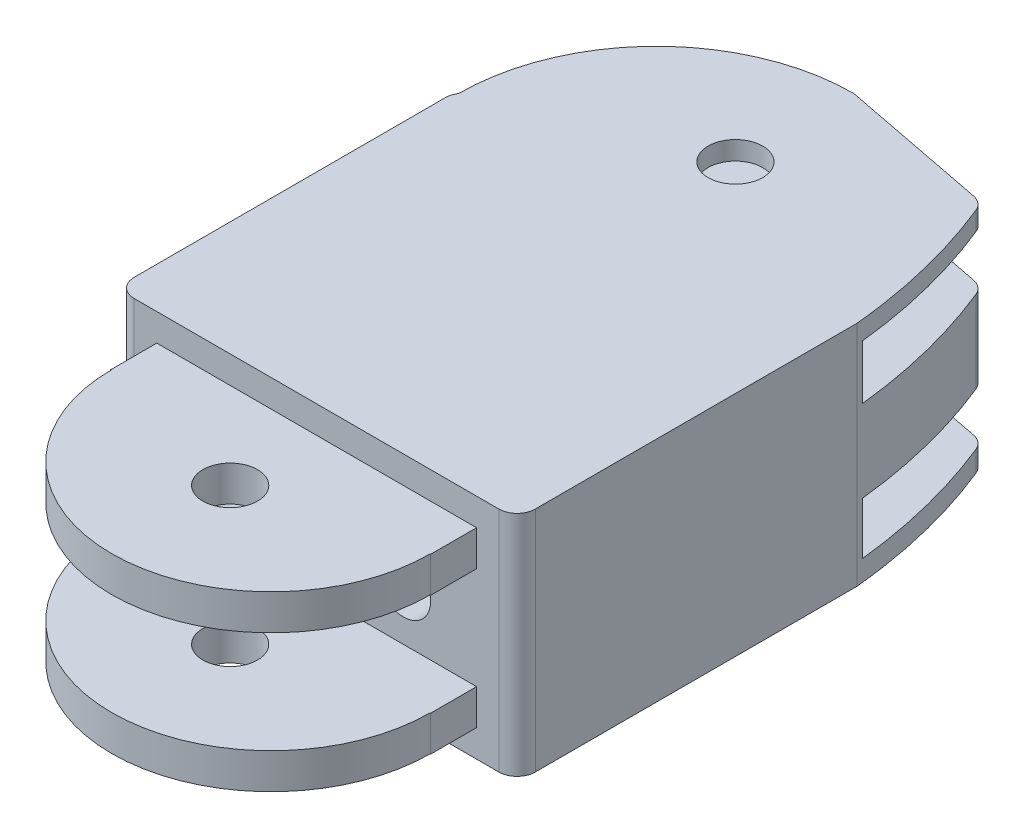
SolidWorks part; units mm, degrees
ref_plane "Front Plane" through (0, 0, 0) normal (0, 0, 1) x (1, 0, 0)
ref_plane "Top Plane" through (0, 0, 0) normal (0, 1, 0) x (1, 0, 0)
ref_plane "Right Plane" through (0, 0, 0) normal (1, 0, 0) x (0, 0, -1)
sketch "Sketch2" plane through (0, 0, 0) normal (0, 0, 1) x (1, 0, 0)
  line L0 (-24.2561, -24.0702) -> (-22.0061, -24.0702) construction
  line L1 (-24.2561, -17.8202) -> (-2.2017, -17.8202) construction
  line L2 (-24.2561, -17.8202) -> (-24.2561, -30.3202) construction
  line L3 (-24.2561, -30.3202) -> (-2.2017, -30.3202) construction
  line L4 (-2.2017, -17.8202) -> (-2.2017, -30.3202) construction
  line L5 (-2.2017, -24.0702) -> (-4.4517, -24.0702) construction
  line L6 (-22.0061, -24.0702) -> (-22.0061, -30.3202) construction
  line L7 (-4.4517, -24.0702) -> (-4.4517, -30.3202) construction
  line L8 (-24.2561, -17.8202) -> (-24.2561, -19.3148) construction
  line L9 (-24.2561, -19.3148) -> (-22.0061, -19.3148) construction
  line L10 (-2.2017, -17.8202) -> (-2.2017, -19.3148) construction
  line L11 (-2.2017, -19.3148) -> (-4.4517, -19.3148) construction
  line L12 (-2.2017, -30.3202) -> (-2.2017, -28.8202) construction
  line L13 (-2.2017, -28.8202) -> (-4.4517, -28.8202) construction
  line L14 (-24.2561, -30.3202) -> (-24.2561, -28.8202) construction
  line L15 (-24.2561, -28.8202) -> (-22.0061, -28.8202) construction
  line L17 (-22.0061, -28.8202) -> (-4.4517, -28.8202)
  line L18 (-22.0061, -28.8202) -> (-22.0061, -26.8702)
  line L19 (-22.0061, -26.8702) -> (-4.4517, -26.8702)
  line L20 (-4.4517, -28.8202) -> (-4.4517, -26.8702)
  line L21 (-22.0061, -28.8202) -> (-4.4517, -26.8702) construction
  line L22 (-22.0061, -26.8702) -> (-4.4517, -28.8202) construction
  line L23 (-22.0061, -19.3148) -> (-4.4517, -19.3148)
  line L24 (-22.0061, -19.3148) -> (-22.0061, -21.2648)
  line L25 (-22.0061, -21.2648) -> (-4.4517, -21.2648)
  line L26 (-4.4517, -19.3148) -> (-4.4517, -21.2648)
  line L27 (-22.0061, -19.3148) -> (-4.4517, -21.2648) construction
  line L28 (-22.0061, -21.2648) -> (-4.4517, -19.3148) construction
  point P19 (-13.2289, -27.8452)
  point P22 (-13.2289, -20.2898)
extrude "Boss-Extrude1" add sketch "Sketch2" along normal blind 8.75
sketch "Sketch3" plane through (0, -19.3148, 0) normal (0, 1, 0) x (1, 0, 0)
  line L0 (-4.4517, 0) -> (-22.0061, 0) construction
  line L1 (-4.4517, -8.75) -> (-22.0061, -8.75) construction
  arc A0 (-13.2289, -8.75) -> (-4.4789, 0) centre (-13.2289, 0) ccw
  arc A1 (-13.2289, -8.75) -> (-21.9789, 0) centre (-13.2289, 0) cw
  spline S0 degree 2 poles (-22.0061, -8.75) (-13.2289, -12.4735) (-4.4517, -8.75) knots 0 0 0 1 1 1
  spline S1 degree 2 poles (-21.9789, 0) (-25.927, -4.2429) (-22.0061, -8.75) knots 0 0 0 1 1 1
  spline S2 degree 2 poles (-4.4789, 0) (1.1383, -4.1517) (-4.4517, -8.75) knots 0 0 0 1 1 1
extrude "Cut-Extrude1" cut sketch "Sketch3" against normal through all contours S0 S2 A0 A1 S1
sketch "Sketch4" plane through (0, 0, 0) normal (0, 0, -1) x (-1, 0, 0)
  line L0 (22.0061, -19.3148) -> (24.2561, -19.3148) construction
  line L1 (22.0061, -19.3148) -> (4.4789, -19.3148) construction
  line L2 (22.0061, -19.3148) -> (22.0061, -28.8202) construction
  line L3 (22.0061, -28.8202) -> (4.4789, -28.8202) construction
  line L4 (4.4789, -19.3148) -> (4.4789, -28.8202) construction
  line L5 (22.0061, -19.3148) -> (4.4789, -28.8202) construction
  line L6 (22.0061, -28.8202) -> (4.4789, -19.3148) construction
  line L7 (24.2561, -19.3148) -> (24.2561, -17.8148) construction
  line L8 (4.4789, -28.8202) -> (2.2289, -28.8202) construction
  line L9 (2.2289, -28.8202) -> (2.2289, -30.3202) construction
  line L11 (24.2561, -17.8148) -> (2.2289, -17.8148)
  line L12 (24.2561, -17.8148) -> (24.2561, -30.3202)
  line L13 (24.2561, -30.3202) -> (2.2289, -30.3202)
  line L14 (2.2289, -17.8148) -> (2.2289, -30.3202)
  line L15 (24.2561, -17.8148) -> (2.2289, -30.3202) construction
  line L16 (24.2561, -30.3202) -> (2.2289, -17.8148) construction
  point P4 (13.2425, -24.0675)
  point P14 (13.2425, -24.0675)
extrude "Boss-Extrude2" add sketch "Sketch4" along normal blind 32 contours L12 L13 L14 L11
sketch "Sketch5" plane through (0, -19.3148, 0) normal (0, 1, 0) x (1, 0, 0)
  line L0 (-13.2289, -8.75) -> (-13.2289, -2.25) construction
  arc A0 (-21.9789, 0) -> (-4.4789, 0) centre (-13.2289, 0) ccw construction
  circle A1 centre (-13.2289, -2.25) radius 1.5
extrude "Cut-Extrude2" cut sketch "Sketch5" against normal blind 12 contours A1
sketch "Sketch6" plane through (0, 0, 0) normal (0, 0, 1) x (1, 0, 0)
  line L0 (-24.2561, -30.3202) -> (-2.2289, -30.3202)
  line L1 (-2.2289, -30.3202) -> (-2.2289, -17.8148)
  line L2 (-2.2289, -17.8148) -> (-24.2561, -17.8148)
  line L3 (-24.2561, -17.8148) -> (-24.2561, -30.3202)
  line L4 (-22.0061, -28.8202) -> (-4.4517, -28.8202)
  line L5 (-4.4517, -28.8202) -> (-4.4517, -26.8702)
  line L6 (-4.4517, -28.8202) -> (-4.4517, -26.8702) construction
  line L7 (-4.4517, -26.8702) -> (-22.0061, -26.8702)
  line L8 (-22.0061, -28.8202) -> (-22.0061, -26.8702)
  line L9 (-22.0061, -21.2648) -> (-22.0061, -19.3148)
  line L10 (-22.0061, -19.3148) -> (-4.4517, -19.3148)
  line L11 (-4.4517, -19.3148) -> (-4.4517, -21.2648)
  line L12 (-4.4517, -21.2648) -> (-22.0061, -21.2648)
extrude "Cut-Extrude3" cut sketch "Sketch6" against normal blind 2.5
sketch "Sketch7" plane through (0, -17.8148, 0) normal (0, 1, 0) x (1, 0, 0)
  line L0 (-13.2425, 32) -> (-13.2425, 25.5) construction
  line L1 (-24.2561, 32) -> (-2.2289, 32) construction
  line L2 (-13.2425, 25.5) -> (-13.2425, 21.1557) construction
  line L3 (-24.0869, 21.1557) -> (-24.2561, 21.1557)
  line L4 (-24.2561, 32) -> (-24.2561, 2.5) construction
  line L6 (-2.2289, 32) -> (-2.2289, 2.5) construction
  line L7 (-13.2425, 32) -> (-4.5527, 30.3114)
  circle A0 centre (-13.2425, 25.5) radius 1.5
  arc A1 (-13.2425, 32) -> (-24.0869, 21.1557) centre (-13.2425, 21.1557) ccw
  spline S0 degree 3 poles (-2.2289, 21.1557) (11.4715, 27.1897) (-11.7652, 53.4313) (-37.0079, 21.5236) (-24.2561, 21.1557) knots 0 0 0 0 0.520113 1 1 1 1
  spline S1 degree 2 poles (-4.5527, 30.3114) (-2.6852, 25.9285) (-2.2289, 21.1557) knots 0 0 0 1 1 1
extrude "Cut-Extrude4" cut sketch "Sketch7" against normal blind 13
sketch "Sketch8" plane through (0, 0, -2.5) normal (0, 0, 1) x (1, 0, 0)
  line L0 (-24.2561, -24.0675) -> (-18.0111, -24.0675) construction
  line L1 (-24.2561, -17.8148) -> (-24.2561, -30.3202) construction
  line L2 (-2.2289, -24.0675) -> (-8.474, -24.0675) construction
  line L3 (-2.2289, -30.3202) -> (-2.2289, -17.8148) construction
  line L4 (-4.4517, -21.2648) -> (-4.4517, -24.0675) construction
  line L5 (-4.4517, -24.0675) -> (-8.474, -24.0675) construction
  circle A0 centre (-18.0111, -24.0675) radius 1.5
  circle A1 centre (-8.474, -24.0675) radius 1.5
extrude "Cut-Extrude5" cut sketch "Sketch8" against normal blind 32 and the other way blind 10
fillet "Fillet3" radius 1 4 edges at (-24.2561, -24.0675, -2.5) (-24.2561, -24.0675, -21.1557) (-2.2289, -24.0675, -2.5) (-4.5527, -24.0675, -30.3114)
ref_plane "Plane4" through (0, 0, -32.5) normal (0, 0, 1) x (1, 0, 0)
sketch "Sketch9" plane through (0, 0, -32.5) normal (0, 0, 1) x (1, 0, 0)
  line L0 (-24.247, -17.8148) -> (-24.247, -18.8384) construction
  line L1 (-24.247, -17.8148) -> (-2.2121, -17.8148) construction
  line L2 (-24.247, -17.8148) -> (-24.247, -30.3202) construction
  line L3 (-24.247, -30.3202) -> (-2.2121, -30.3202) construction
  line L4 (-2.2121, -17.8148) -> (-2.2121, -30.3202) construction
  line L5 (-24.247, -17.8148) -> (-2.2121, -30.3202) construction
  line L6 (-24.247, -30.3202) -> (-2.2121, -17.8148) construction
  line L7 (-24.247, -30.3202) -> (-24.247, -29.1818) construction
  line L8 (-24.247, -18.8384) -> (-2.2121, -18.8384)
  line L9 (-24.247, -18.8384) -> (-24.247, -21.8148)
  line L10 (-24.247, -21.8148) -> (-2.2121, -21.8148)
  line L11 (-2.2121, -18.8384) -> (-2.2121, -21.8148)
  line L12 (-24.247, -18.8384) -> (-2.2121, -21.8148) construction
  line L13 (-24.247, -21.8148) -> (-2.2121, -18.8384) construction
  line L14 (-13.2295, -21.8148) -> (-13.2295, -24.0675) construction
  line L15 (-24.247, -29.1818) -> (-2.2121, -29.1818)
  line L16 (-24.247, -29.1818) -> (-24.247, -26.3202)
  line L17 (-24.247, -26.3202) -> (-2.2121, -26.3202)
  line L18 (-2.2121, -29.1818) -> (-2.2121, -26.3202)
  line L19 (-24.247, -29.1818) -> (-2.2121, -26.3202) construction
  line L20 (-24.247, -26.3202) -> (-2.2121, -29.1818) construction
  line L21 (-13.2295, -24.0675) -> (-13.2295, -26.3202) construction
  point P4 (-13.2295, -24.0675)
  point P8 (-13.2295, -20.3266)
  point P13 (-13.2295, -27.751)
  point P16 (0, 0)
  point P18 (0, 0)
  point P19 (-24.26, -18.8384)
  point P20 (0, 0)
  point P22 (-24.247, -29.1818)
extrude "Cut-Extrude6" cut sketch "Sketch9" along normal blind 11
sketch "Sketch10" plane through (0, 0, -21.5) normal (0, 0, -1) x (-1, 0, 0)
  line L0 (24.0814, -21.8148) -> (2.2637, -21.8148) construction
  line L1 (3.8875, -21.8148) -> (21.8097, -21.8148)
  line L2 (3.8875, -21.8148) -> (3.8875, -18.8384)
  line L3 (3.8875, -18.8384) -> (21.8097, -18.8384)
  line L4 (21.8097, -21.8148) -> (21.8097, -18.8384)
  line L5 (3.8875, -21.8148) -> (21.8097, -18.8384) construction
  line L6 (3.8875, -18.8384) -> (21.8097, -21.8148) construction
  line L7 (2.2637, -18.8384) -> (24.0814, -18.8384) construction
  line L8 (24.0814, -29.1818) -> (2.2637, -29.1818) construction
  line L9 (21.8097, -29.1818) -> (3.8875, -29.1818)
  line L10 (21.8097, -29.1818) -> (21.8097, -26.3202)
  line L11 (21.8097, -26.3202) -> (3.8875, -26.3202)
  line L12 (3.8875, -29.1818) -> (3.8875, -26.3202)
  line L13 (21.8097, -29.1818) -> (3.8875, -26.3202) construction
  line L14 (21.8097, -26.3202) -> (3.8875, -29.1818) construction
  line L15 (2.2637, -26.3202) -> (24.0814, -26.3202) construction
  point P4 (12.8486, -20.3266)
  point P13 (12.8486, -27.751)
extrude "Cut-Extrude7" cut sketch "Sketch10" against normal blind 5
